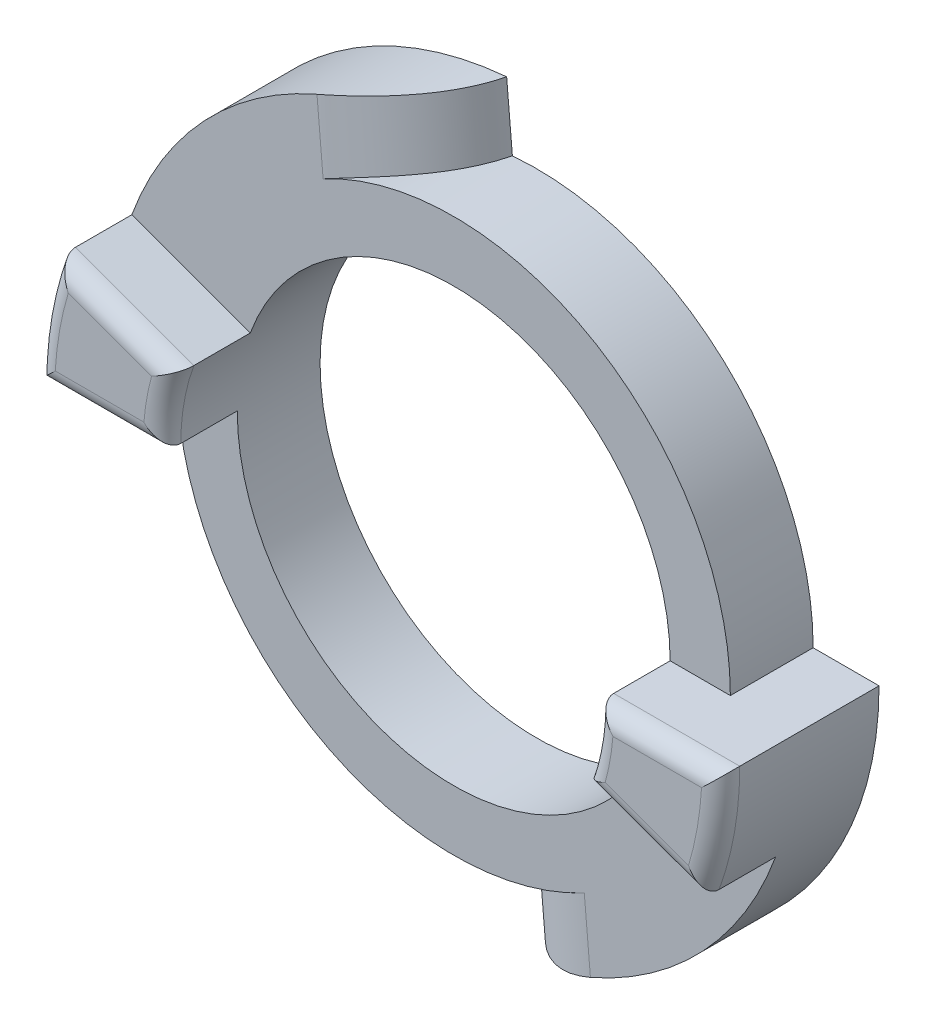
SolidWorks part; units mm, degrees
ref_plane "Front Plane" through (0, 0, 0) normal (0, 0, 1) x (1, 0, 0)
ref_plane "Top Plane" through (0, 0, 0) normal (0, 1, 0) x (1, 0, 0)
ref_plane "Right Plane" through (0, 0, 0) normal (1, 0, 0) x (0, 0, -1)
sketch "Sketch3" plane through (0, 0, 0) normal (0, 0, 1) x (1, 0, 0)
  line L0 (0, 0) -> (-11.3556, 4.1331)
  line L1 (0, 0) -> (14.7514, -5.3691)
  line L2 (7.5, 0) -> (9.25, 0) construction
  line L3 (-7.5, 0) -> (-9.25, 0) construction
  line L4 (0, 0) -> (-9.858, 0)
  line L5 (0, 0) -> (9.5492, 0)
  line L6 (0, 0) -> (-0.832, 9.5095)
  line L7 (0, 7.5) -> (0, 9.25) construction
  line L8 (0, 0) -> (0.8418, -9.6214)
  line L9 (0, -7.5) -> (0, -9.25) construction
  circle A2 centre (0, 0) radius 9.1
  circle A3 centre (0, 0) radius 5.75
  circle A4 centre (0, 0) radius 7.35
  line M12 (-3.5507, -6.15) -> (-7.1014, 0)
  line M13 (-7.1014, 0) -> (-3.5507, 6.15)
  line M14 (-3.5507, 6.15) -> (3.5507, 6.15)
  line M15 (3.5507, 6.15) -> (7.1014, 0)
  line M16 (7.1014, 0) -> (3.5507, -6.15)
  line M17 (3.5507, -6.15) -> (-3.5507, -6.15)
  dimension "D1" = 14.7
  dimension "D2" = 18.2
  dimension "D5" = 11.5
  dimension "D3" = 20
  dimension "D4" = 20
  dimension "D6" = 5
  dimension "D7" = 5
extrude "Boss-Extrude1" add sketch "Sketch3" along normal blind 2.2 contours A4 L0 A2 L4 | A4 L6 A2 L0 | L5 A4 L6 M14 M15 | A3 L5 L6 M15 M14 | A3 L6 L0 M14 M13 | L6 A4 L0 M13 M14 | L0 A4 L4 M13 | A3 L0 L4 M13 | L1 A4 L5 M16 | A3 L1 L5 M16 | L8 A4 L1 M16 M17 | A3 L8 L1 M17 M16 | L4 A4 L8 M17 M12 | A3 L4 L8 M12 M17 | A4 L8 A2 L1 | A4 L1 A2 L5 region at (-6.1284, 0.8701, 0) region at (-3.3427, 4.8969, 0) region at (6.1284, -0.8701, 0) region at (3.3427, -4.8969, 0) region at (-3.9509, -4.3117, 0) region at (3.9509, 4.3117, 0) region at (-6.7655, 1.3999, 0) region at (-6.3594, 2.402, 0) region at (6.7655, -1.3999, 0) region at (6.3594, -2.402, 0) region at (-5.4201, -3.1293, 0) region at (5.4201, 3.1293, 0) region at (-8.0894, 1.4264, 0) region at (-4.7607, 6.2043, 0) region at (8.0894, -1.4264, 0) region at (4.7607, -6.2043, 0)
sketch "Sketch4" plane through (0, 0, 2.2) normal (0, 0, 1) x (1, 0, 0)
  line L0 (0, 0) -> (9.1, 0)
  line L1 (0, 0) -> (-9.1, 0)
  line L2 (0, 0) -> (-9.0753, 3.3031)
  line L3 (0, 0) -> (8.948, -3.2568)
  circle A0 centre (0, 0) radius 9.1
  circle A1 centre (0, 0) radius 5.75 construction
  circle A2 centre (0, 0) radius 5.75
  arc M5 (0.7931, -9.0654) -> (9.1, 0) centre (0, 0) ccw
  line M6 (9.1, 0) -> (7.35, 0)
  arc M9 (-0.7931, 9.0654) -> (-9.1, 0) centre (0, 0) ccw
  line M10 (-9.1, 0) -> (-7.35, 0)
  circle M13 centre (0, 0) radius 5.75
  dimension "D1" = 20
  dimension "D2" = 20
extrude "Boss-Extrude2" add sketch "Sketch4" along normal blind 2 contours L2 L1 M13 M9 M10 | L3 L0 M13 M5 M6 region at (7.3985, -1.3046, 2.2) region at (-7.3985, 1.3046, 2.2)
fillet "Fillet1" radius 0.5 8 edges at (-5.6626, 0.9985, 4.2) (-6.9772, 2.5395, 4.2) (-8.9618, 1.5802, 4.2) (-7.425, 0, 4.2) (5.6626, -0.9985, 4.2) (6.9772, -2.5395, 4.2) (8.9618, -1.5802, 4.2) (7.425, 0, 4.2)
fillet "Fillet2" radius 3 2 edges at (0.7169, -8.1937, 2.2) (-0.7169, 8.1937, 2.2)
